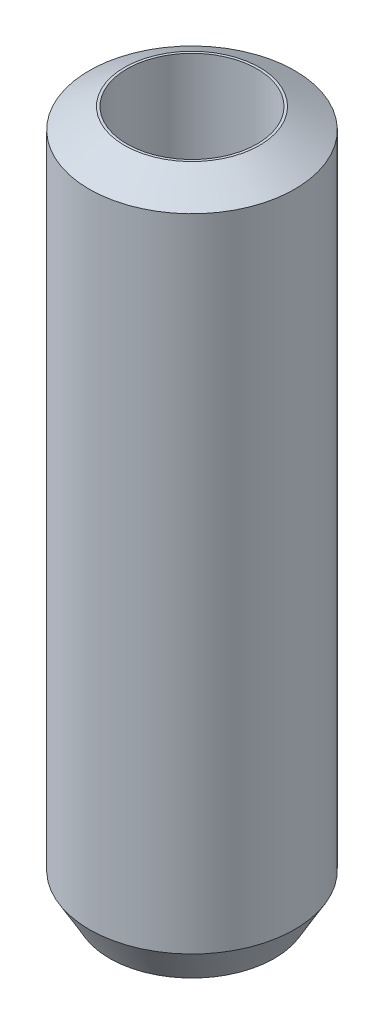
SolidWorks part; units mm, degrees
ref_plane "Front Plane" through (0, 0, 0) normal (0, 0, 1) x (1, 0, 0)
ref_plane "Top Plane" through (0, 0, 0) normal (0, 1, 0) x (1, 0, 0)
ref_plane "Right Plane" through (0, 0, 0) normal (1, 0, 0) x (0, 0, -1)
sketch "Sketch1" plane through (0, 0, 0) normal (0, 1, 0) x (1, 0, 0)
  circle A0 centre (0, 0) radius 17.5
  dimension "SHAFT_OD" = 35
extrude "Boss-Extrude1" add sketch "Sketch1" along normal blind 118.6221
sketch "Sketch2" plane through (0, 0, 0) normal (0, 1, 0) x (1, 0, 0)
  circle A0 centre (0, 0) radius 11.0839
  dimension "BORE_D" = 22.1678
extrude "Cut-Extrude1" cut sketch "Sketch2" along normal through all
chamfer "Chamfer1" distance 3.461 angle 60 2 edges at (0, 118.6221, 17.5) (0, 0, 17.5) first distance on face at (0, 118.6221, 17.5) first distance on face at (0, 0, 11.0839)
